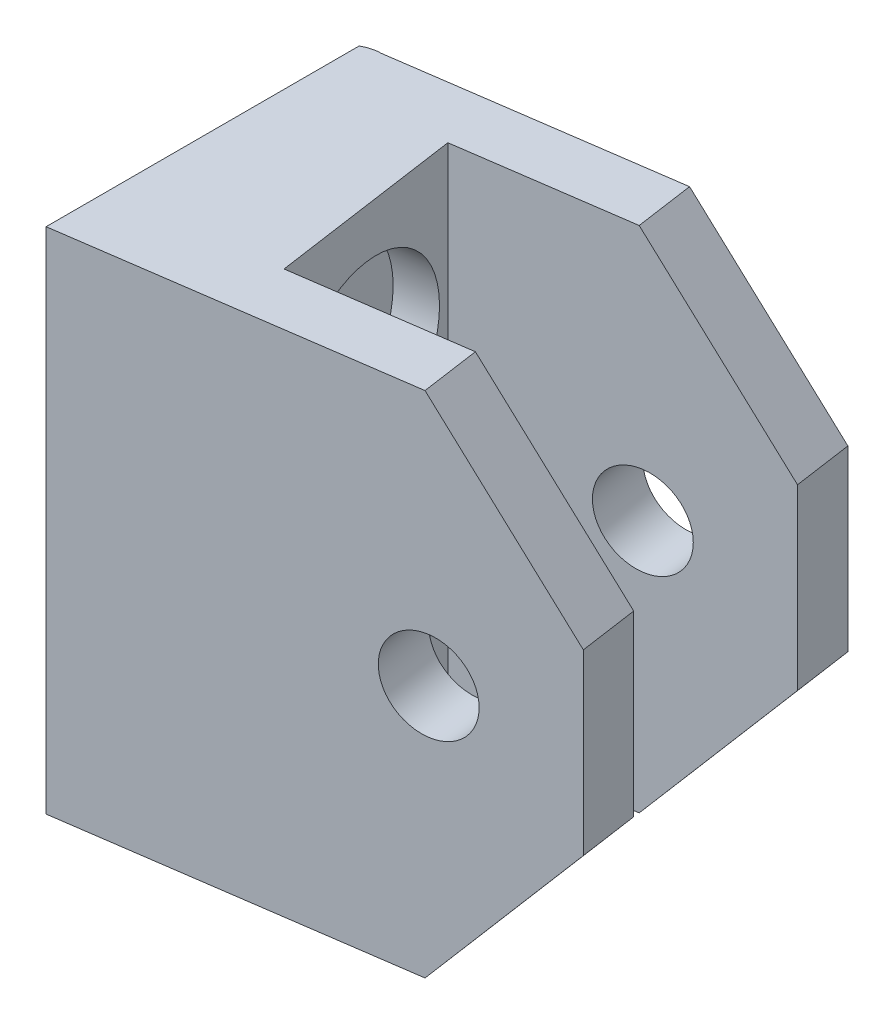
SolidWorks part; units mm, degrees
material "6061-T6 (SS)"
ref_plane "X-Y Datum" through (0, 0, 0) normal (0, 0, 1) x (1, 0, 0)
ref_plane "X-Z Datum" through (0, 0, 0) normal (0, 1, 0) x (1, 0, 0)
ref_plane "Y-Z Datum" through (0, 0, 0) normal (1, 0, 0) x (0, 0, -1)
sketch "Sketch1" plane through (0, 0, 0) normal (0, 1, 0) x (1, 0, 0)
  line L10 (43.5767, 6.2522) -> (0, 0)
  line L11 (31.488, -12.3281) -> (6.9122, -15.8541) construction
  line L12 (31.488, -12.3281) -> (37.2397, -52.4164) construction
  line L13 (47.4113, -20.4743) -> (14.7261, -25.1639)
  line L14 (14.7261, -25.1639) -> (11.7933, -4.723)
  line L15 (11.7933, -4.723) -> (44.4786, -0.0334)
  line L16 (47.4113, -20.4743) -> (48.3132, -26.7599)
  line L17 (48.3132, -26.7599) -> (-0.0216, -33.6948)
  line L19 (44.4786, -0.0334) -> (43.5767, 6.2522)
  line L23 (-1.905, -33.8451) -> (-1.905, 10.9886) construction
  line L24 (-1.905, -0.5148) -> (-1.905, -33.8451)
  line L25 (-0.0216, -33.6948) -> (-1.905, -33.965)
  line L26 (-1.905, -33.965) -> (-1.905, -33.8451)
  arc A0 (0, 0) -> (-1.905, -0.5148) centre (0, -3.7822) ccw
  point P0 (31.488, -12.3281)
  point P14 (0, 0)
  dimension "D1" = 18.415
  dimension "D2" = 31.488
  dimension "D3" = 50.7324
  dimension "D5" = 10.3251
  dimension "D6" = 10.3251
  dimension "D7" = 14.605
  dimension "D8" = 6.35
  dimension "D9" = 6.35
extrude "Boss-Extrude1" add sketch "Sketch1" along normal blind 54.3789
sketch "Sketch6" plane through (4.7364, 0, 33.0121) normal (0.142, 0, 0.9899) x (0.9899, 0, -0.142)
  line L0 (-6.7095, 54.3789) -> (44.023, 54.3789) construction
  line L1 (44.023, 36.7144) -> (29.0719, 54.3789)
  line L2 (44.023, 54.3789) -> (44.023, 0) construction
  line L3 (29.0719, 54.3789) -> (44.023, 54.3789)
  line L4 (44.023, 54.3789) -> (44.023, 36.7144)
  line L5 (29.418, 27.1894) -> (40.6527, 27.1894) construction
  line L6 (44.023, 0) -> (44.023, 17.6644)
  line L7 (29.0719, 0) -> (44.023, 0)
  line L8 (44.023, 17.6644) -> (29.0719, 0)
  circle A0 centre (29.418, 27.1894) radius 4.7625
  dimension "D1" = 9.525
  dimension "D2" = 27.1894
  dimension "D3" = 19.05
extrude "Cut-Extrude2" cut sketch "Sketch6" against normal through all
sketch "Sketch16" plane through (10.8914, 0, -1.5627) normal (0.9899, 0, -0.142) x (-0.142, 0, -0.9899)
  line L0 (-27.0002, 27.1894) -> (-6.35, 27.1894) construction
  line L1 (-16.6751, 54.3789) -> (-16.6751, 0) construction
  line L4 (-27.0002, 0) -> (-6.35, 0)
  line L5 (-6.35, 0) -> (-6.35, 54.3789)
  line L6 (-6.35, 54.3789) -> (-27.0002, 54.3789)
  line L7 (-27.0002, 54.3789) -> (-27.0002, 0)
  line L8 (-27.0002, 0) -> (-6.35, 0) construction
  line L9 (-6.35, 0) -> (-6.35, 54.3789) construction
  line L10 (-6.35, 54.3789) -> (-27.0002, 54.3789) construction
  line L11 (-27.0002, 54.3789) -> (-27.0002, 0) construction
  point P8 (-16.6751, 14.4894)
  point P9 (-16.6751, 39.8894)
  dimension "D2" = 12.7
  dimension "D3" = 25.4
  dimension "D1" = 0
hole_wizard "CBORE for M6 Hex Head Bolt1" positions "Sketch17" profile "Sketch18" counterbore size "M6" standard "ANSI Metric" end condition through all
sketch "Sketch17" plane through (10.8914, 0, -1.5627) normal (0.9899, 0, -0.142) x (-0.142, 0, -0.9899)
  point P0 (-16.6751, 39.8894)
  point P3 (-16.6751, 14.4894)
sketch "Sketch18" plane through (13.2597, 39.8894, 14.9434) normal (0, 1, 0) x (-0.142, 0, -0.9899)
  line L0 (0, 0) -> (0, 17.7124)
  line L1 (0, 17.7124) -> (3.3, 17.7124)
  line L3 (3.3, 17.7124) -> (3.3, 4.38)
  line L4 (3.3, 4.38) -> (9.275, 4.38)
  line L5 (9.275, 4.38) -> (9.275, 0)
  line L7 (9.275, 0) -> (0, 0)
  line L11 (0, -6.35) -> (0, 107.95) construction
  dimension "Thru Hole Dia." = 6.6
  dimension "Thru Hole Depth" = 17.7124
  dimension "C'Bore Dia." = 18.55
  dimension "C'Bore Depth" = 4.38
